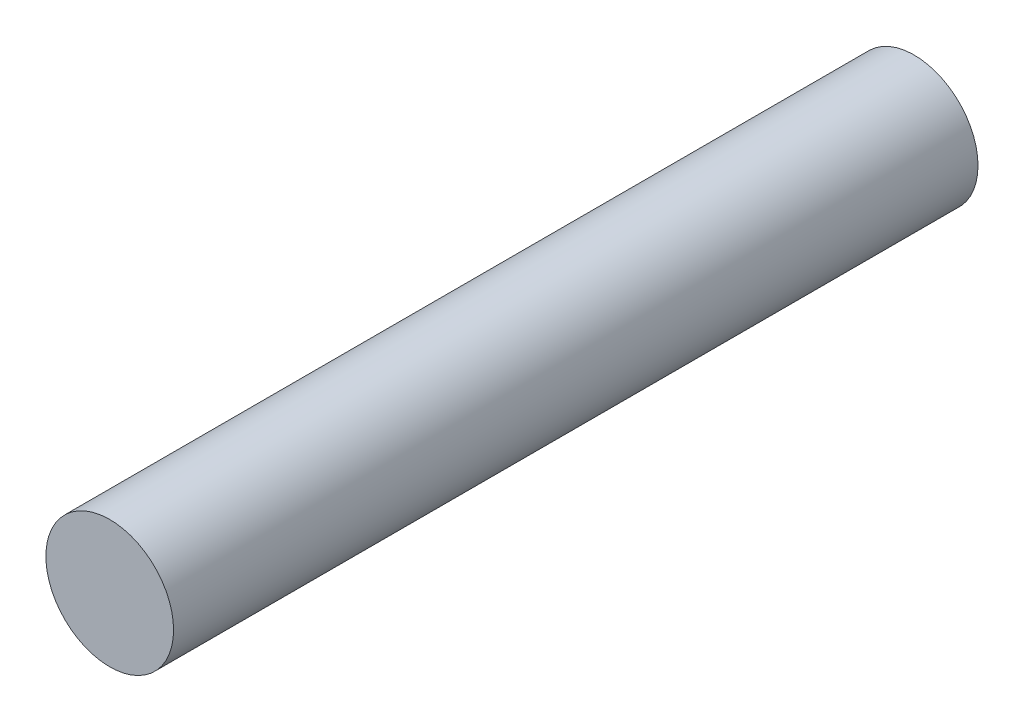
SolidWorks part; units mm, degrees
material "Paracadute"
ref_plane "Piano frontale" through (0, 0, 0) normal (0, 0, 1) x (1, 0, 0)
ref_plane "Piano superiore" through (0, 0, 0) normal (0, 1, 0) x (1, 0, 0)
ref_plane "Piano destro" through (0, 0, 0) normal (1, 0, 0) x (0, 0, -1)
sketch "Schizzo1" plane through (0, 0, 0) normal (0, 0, 1) x (1, 0, 0)
  circle A0 centre (0, 0) radius 50
  dimension "D1" = 100
extrude "Estrusione-Estrusione1" add sketch "Schizzo1" along normal blind 630
